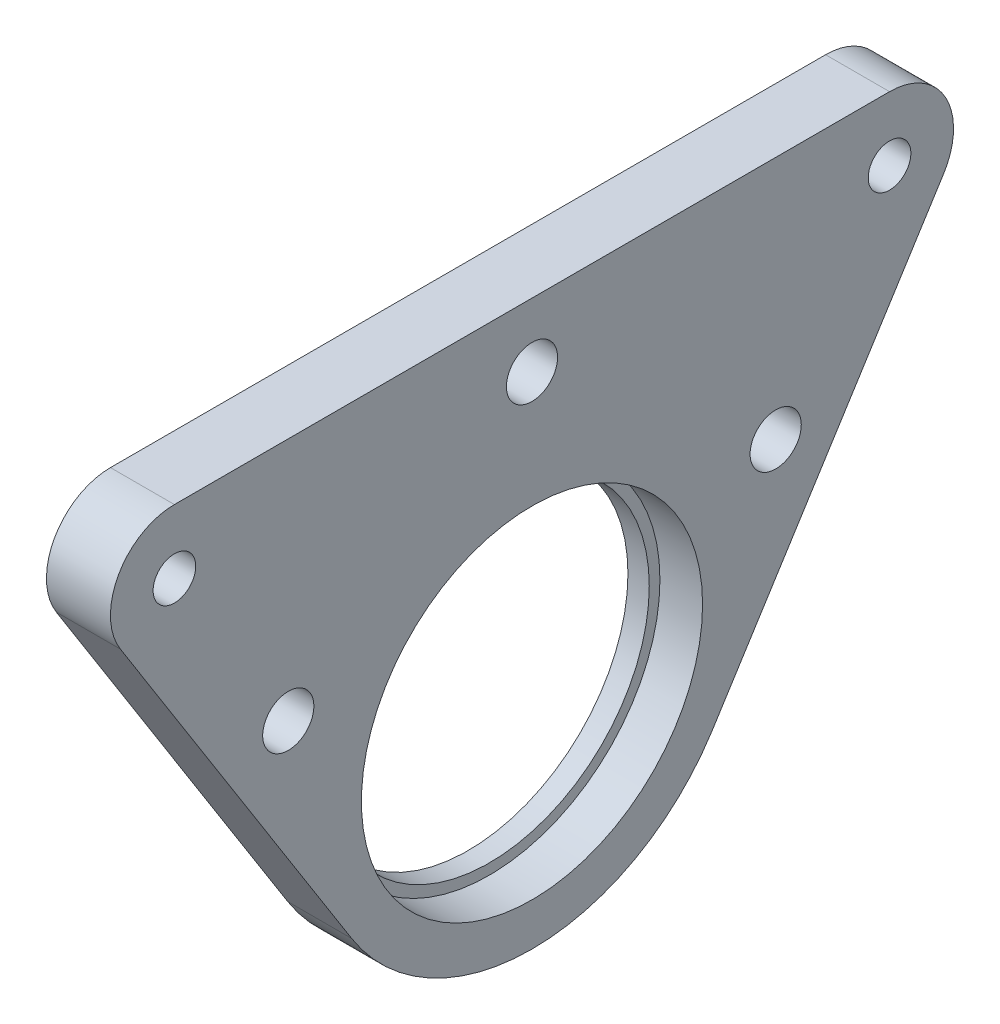
SolidWorks part; units mm, degrees
ref_plane "Front Plane" through (0, 0, 0) normal (0, 0, 1) x (1, 0, 0)
ref_plane "Top Plane" through (0, 0, 0) normal (0, 1, 0) x (1, 0, 0)
ref_plane "Right Plane" through (0, 0, 0) normal (1, 0, 0) x (0, 0, -1)
sketch "Sketch1" plane through (0, 0, 0) normal (1, 0, 0) x (0, 0, -1)
  circle A0 centre (0, 0) radius 15
  circle A1 centre (0, 0) radius 20
  dimension "D1" = 30
  dimension "D2" = 40
extrude "Boss-Extrude1" add sketch "Sketch1" along normal blind 2
sketch "Sketch2" plane through (2, 0, 0) normal (1, 0, 0) x (0, 0, -1)
  circle A0 centre (0, 0) radius 16
  circle A1 centre (0, 0) radius 20 construction
  circle A2 centre (0, 0) radius 20
  dimension "D1" = 32
extrude "Boss-Extrude2" add sketch "Sketch2" along normal blind 4
sketch "Sketch3" plane through (6, 0, 0) normal (1, 0, 0) x (0, 0, -1)
  line L0 (-33.5359, 26.8817) -> (0, 0) construction
  line L1 (0, 0) -> (33.5359, 26.8817) construction
  line L2 (-38.6088, 23.6778) -> (-16.9099, -10.6797)
  line L3 (-33.5359, 32.8817) -> (33.5359, 32.8817)
  line L4 (16.9099, -10.6797) -> (38.6088, 23.6778)
  circle A0 centre (-33.5359, 26.8817) radius 2
  circle A1 centre (33.5359, 26.8817) radius 2
  arc A2 (-33.5359, 32.8817) -> (-38.6088, 23.6778) centre (-33.5359, 26.8817) ccw
  arc A3 (38.6088, 23.6778) -> (33.5359, 32.8817) centre (33.5359, 26.8817) ccw
  circle A4 centre (0, 0) radius 20 construction
  arc A5 (16.9099, -10.6797) -> (-16.9099, -10.6797) centre (0, 0) ccw
  circle A6 centre (-33.5359, 26.8817) radius 6 construction
  circle A7 centre (33.5359, 26.8817) radius 6 construction
  dimension "D1" = 4
  dimension "D2" = 102.57
  dimension "D3" = 42.98
  dimension "D4" = 4
extrude "Boss-Extrude3" add sketch "Sketch3" against normal up to surface (6 mm away) up to face at (0, 0, -20)
sketch "Sketch4" plane through (6, 0, 0) normal (1, 0, 0) x (0, 0, -1)
  line L0 (-33.5359, 26.8817) -> (-22.8562, 9.9718) construction
  line L1 (-38.6088, 23.6778) -> (-16.9099, -10.6797) construction
  line L2 (0, 0) -> (0, 15) construction
  line L3 (33.5359, 26.8817) -> (22.8562, 9.9718) construction
  circle A0 centre (-22.8562, 9.9718) radius 2.4
  circle A2 centre (0, 0) radius 15 construction
  circle A3 centre (22.8562, 9.9718) radius 2.4
  circle A4 centre (0, 26.8817) radius 2.4
  dimension "D1" = 4.8
  dimension "D2" = 20
extrude "Cut-Extrude1" cut sketch "Sketch4" against normal up to surface (6 mm away) up to face at (0, 14.2393, 0)
